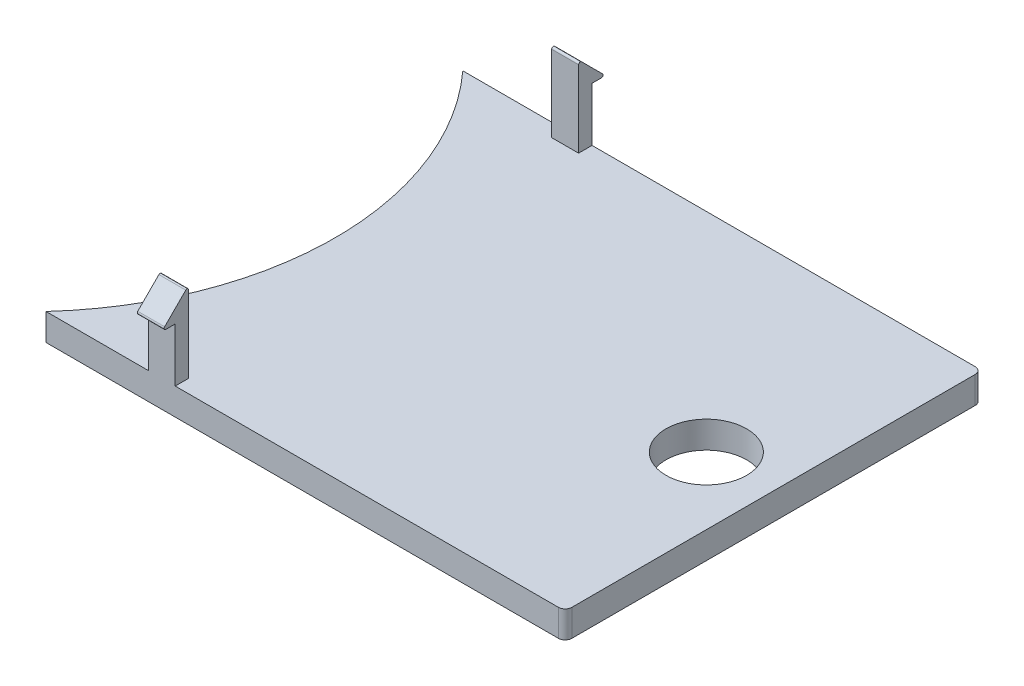
SolidWorks part; units mm, degrees
ref_plane "前视基准面" through (0, 0, 0) normal (0, 0, 1) x (1, 0, 0)
ref_plane "上视基准面" through (0, 0, 0) normal (0, 1, 0) x (1, 0, 0)
ref_plane "右视基准面" through (0, 0, 0) normal (1, 0, 0) x (0, 0, -1)
other "Configuration Table"
sketch "草图1" plane through (0, 0, 0) normal (0, 1, 0) x (1, 0, 0)
  line L0 (37.61, 31) -> (-38.61, 31)
  line L1 (-38.61, 31) -> (-38.61, -31)
  line L2 (-38.61, -31) -> (37.61, -31)
  line L3 (38.61, 30) -> (38.61, -30)
  line L5 (38.61, 0) -> (-38.61, 0) construction
  arc A0 (37.61, 31) -> (38.61, 30) centre (37.61, 30) cw
  arc A1 (37.61, -31) -> (38.61, -30) centre (37.61, -30) ccw
  circle A3 centre (-72.5953, 0) radius 46
  point P8 (0, 0)
  point P9 (0, 0)
  point P14 (-31.9792, -7.9879)
  point P15 (50.1191, -52.9879)
  point P16 (13.9941, -30.8186)
  point P17 (-36.7468, 0)
  point P18 (0, 0)
  point P19 (108.7638, -2.7941)
  point P20 (-85.1417, -4.955)
  point P21 (0, 0)
  point P22 (0, 0)
  point P24 (0, 0)
  dimension "D1" = 1
  dimension "D2" = 1
  dimension "D6" = 92
  dimension "D3" = 77.22
  dimension "D4" = 62
extrude "凸台-拉伸1" add sketch "草图1" along normal blind 4 contours L5 L3 A0 L0 A3 | L3 L5 A3 L2 A1 region at (4.0307, 0, -15.9339) region at (4.0307, 0, 15.9339)
ref_plane "卡扣拉伸基准面" through (-21.39, 0, 0) normal (1, 0, 0) x (0, 0, -1)
sketch "草图3" plane through (-21.39, 0, 0) normal (1, 0, 0) x (0, 0, -1)
  line L0 (-31, 4) -> (-31, 12)
  line L1 (30, 4) -> (-30, 4) construction
  line L2 (-31, 12) -> (-33, 12)
  line L3 (-33, 12) -> (-29, 16)
  line L4 (-29, 16) -> (-29, 4)
  line L5 (-29, 4) -> (-31, 4)
  line L7 (-31, 4) -> (-31, 0) construction
  dimension "D1" = 2
  dimension "D2" = 8
  dimension "D3" = 2
  dimension "D4" = 4
extrude "卡扣-凸台-拉伸" add sketch "草图3" along normal blind 2 and the other way blind 2
fillet "圆角1" radius 0.25 2 edges at (-21.39, 16, 29) (-21.39, 12, 33)
mirror "镜向1" about plane through (0, 0, 0) normal (0, 0, 1) of "圆角1", "卡扣-凸台-拉伸"
sketch "草图4" plane through (0, 0, 0) normal (0, -1, 0) x (1, 0, 0)
  line L0 (0, 0) -> (38.61, 0) construction
  line L1 (38.61, -30) -> (38.61, 30) construction
  circle A0 centre (28.61, 0) radius 6
  dimension "D1" = 12
  dimension "D2" = 10
extrude "切除-拉伸2" cut sketch "草图4" against normal through all
